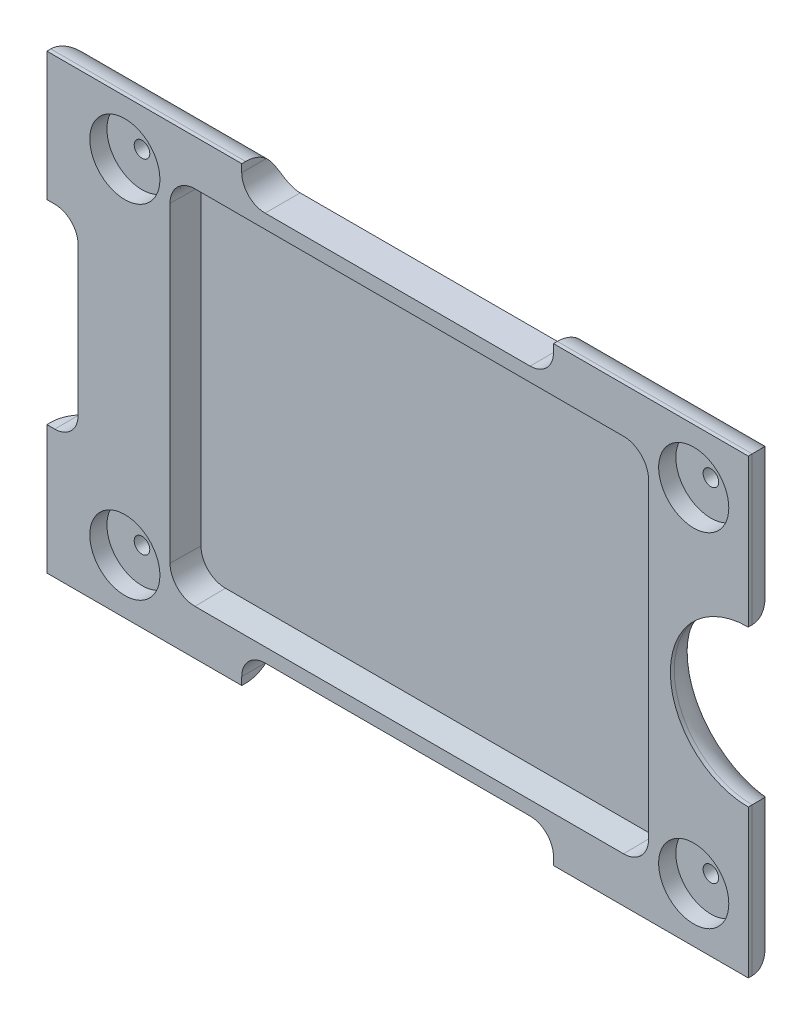
SolidWorks part; units mm, degrees
ref_plane "Front" through (0, 0, 0) normal (0, 0, 1) x (1, 0, 0)
ref_plane "Top" through (0, 0, 0) normal (0, 1, 0) x (1, 0, 0)
ref_plane "Right" through (0, 0, 0) normal (1, 0, 0) x (0, 0, -1)
sketch "Çizim4" plane through (0, 0, 0) normal (0, 0, 1) x (1, 0, 0)
  line L0 (200.6061, -119.4678) -> (200.6061, -100.4678)
  line L1 (111.6061, -77.9678) -> (110.6061, -77.9678)
  line L2 (200.6061, -61.4678) -> (175.6061, -61.4678)
  line L3 (110.6061, -61.4678) -> (110.6061, -77.9678)
  line L4 (110.6061, -119.4678) -> (135.6061, -119.4678)
  line L5 (200.6061, -80.4678) -> (200.6061, -61.4678)
  line L6 (175.6061, -118.4678) -> (175.6061, -119.4678)
  line L7 (175.6061, -119.4678) -> (200.6061, -119.4678)
  line L8 (135.6061, -118.4678) -> (135.6061, -119.4678)
  line L9 (135.6061, -62.4678) -> (135.6061, -61.4678)
  line L10 (138.6061, -115.4678) -> (172.6061, -115.4678)
  line L12 (111.6061, -102.9678) -> (110.6061, -102.9678)
  line L13 (110.6061, -102.9678) -> (110.6061, -119.4678)
  line L15 (114.6061, -80.9678) -> (114.6061, -99.9678)
  line L16 (172.6061, -65.4678) -> (138.6061, -65.4678)
  line L17 (175.6061, -62.4678) -> (175.6061, -61.4678)
  line L18 (135.6061, -61.4678) -> (110.6061, -61.4678)
  arc A0 (138.6061, -65.4678) -> (135.6061, -62.4678) centre (138.6061, -62.4678) cw
  arc A1 (172.6061, -65.4678) -> (175.6061, -62.4678) centre (172.6061, -62.4678) ccw
  arc A2 (175.6061, -118.4678) -> (172.6061, -115.4678) centre (172.6061, -118.4678) ccw
  arc A3 (135.6061, -118.4678) -> (138.6061, -115.4678) centre (138.6061, -118.4678) cw
  arc A4 (114.6061, -99.9678) -> (111.6061, -102.9678) centre (111.6061, -99.9678) cw
  arc A5 (114.6061, -80.9678) -> (111.6061, -77.9678) centre (111.6061, -80.9678) ccw
  arc A6 (200.6061, -80.4678) -> (200.6061, -100.4678) centre (200.6061, -90.4678) ccw
  point P31 (123.1061, -119.4678)
  dimension "D14" = 0
  dimension "D7" = 20
  dimension "D19" = 3
  dimension "D2" = 25
  dimension "D3" = 58
  dimension "D4" = 4
  dimension "D5" = 4
  dimension "D6" = 4
  dimension "D8" = 0
  dimension "D9" = 0
  dimension "D10" = 25
  dimension "D11" = 25
  dimension "D12" = 40
  dimension "D13" = 40
  dimension "D15" = 25
  dimension "D16" = 29
  dimension "D17" = 25
  dimension "D18" = 16.5
extrude "Yükseklik-Ekstrüzyon1" add sketch "Çizim4" along normal blind 4.5
sketch "Çizim6" plane through (0, 0, 4.5) normal (0, 0, 1) x (1, 0, 0)
  line L1 (129.6061, -67.4678) -> (184.6061, -67.4678)
  line L2 (126.6061, -70.4678) -> (126.6061, -110.4678)
  line L3 (129.6061, -113.4678) -> (184.6061, -113.4678)
  line L4 (187.6061, -70.4678) -> (187.6061, -110.4678)
  line L5 (135.6061, -61.4678) -> (110.6061, -61.4678) construction
  line L6 (110.6061, -102.9678) -> (110.6061, -119.4678) construction
  line L7 (110.6061, -119.4678) -> (135.6061, -119.4678) construction
  arc A0 (184.6061, -113.4678) -> (187.6061, -110.4678) centre (184.6061, -110.4678) ccw
  arc A1 (184.6061, -67.4678) -> (187.6061, -70.4678) centre (184.6061, -70.4678) cw
  arc A2 (126.6061, -110.4678) -> (129.6061, -113.4678) centre (129.6061, -110.4678) ccw
  arc A3 (126.6061, -70.4678) -> (129.6061, -67.4678) centre (129.6061, -70.4678) cw
  dimension "D5" = 3
  dimension "D1" = 6
  dimension "D2" = 16
  dimension "D3" = 6
  dimension "D4" = 61
extrude "Kes-Ekstrüzyon2" cut sketch "Çizim6" against normal blind 3.9
sketch "Çizim7" plane through (0, 0, 4.5) normal (0, 0, 1) x (1, 0, 0)
  line L0 (200.6061, -61.4678) -> (175.6061, -61.4678) construction
  line L3 (175.6061, -119.4678) -> (200.6061, -119.4678) construction
  line L6 (200.6061, -80.4678) -> (200.6061, -61.4678) construction
  line L7 (200.6061, -119.4678) -> (200.6061, -100.4678) construction
  circle A0 centre (193.6061, -68.4678) radius 4.5
  circle A1 centre (193.6061, -112.4678) radius 4.5
  circle A2 centre (120.6061, -68.4678) radius 4.5
  circle A3 centre (120.6061, -112.4678) radius 4.5
  dimension "D1" = 9
  dimension "D6" = 9
  dimension "D2" = 7
  dimension "D3" = 7
  dimension "D4" = 7
  dimension "D5" = 7
  dimension "D7" = 73
extrude "Kes-Ekstrüzyon3" cut sketch "Çizim7" against normal blind 2.2
sketch "Çizim9" plane through (0, 0, 2.3) normal (0, 0, 1) x (1, 0, 0)
  circle A0 centre (193.6061, -68.4678) radius 1
  circle A1 centre (193.6061, -112.4678) radius 1
  circle A2 centre (120.6061, -68.4678) radius 1
  circle A3 centre (120.6061, -112.4678) radius 1
  dimension "D1" = 2
  dimension "D2" = 2
extrude "Kes-Ekstrüzyon4" cut sketch "Çizim9" against normal blind 2
fillet "Radyus4" radius 4 9 edges at (123.1061, -61.4678, 0) (110.6061, -111.2178, 0) (123.1061, -119.4678, 0) (188.1061, -119.4678, 0) (188.1061, -61.4678, 0) (110.6061, -69.7178, 0) (200.6061, -70.9678, 0) (190.6061, -90.4678, 0) (200.6061, -109.9678, 0)
chamfer "Pah1" distance 0.2 angle 89 8 edges at (186.7275, -68.3465, 4.5) (187.6061, -90.4678, 4.5) (186.7275, -112.5891, 4.5) (157.1061, -113.4678, 4.5) (127.4848, -112.5891, 4.5) (126.6061, -90.4678, 4.5) (127.4848, -68.3465, 4.5) (157.1061, -67.4678, 4.5) first distance on face at (198.1061, -112.4678, 4.5)
